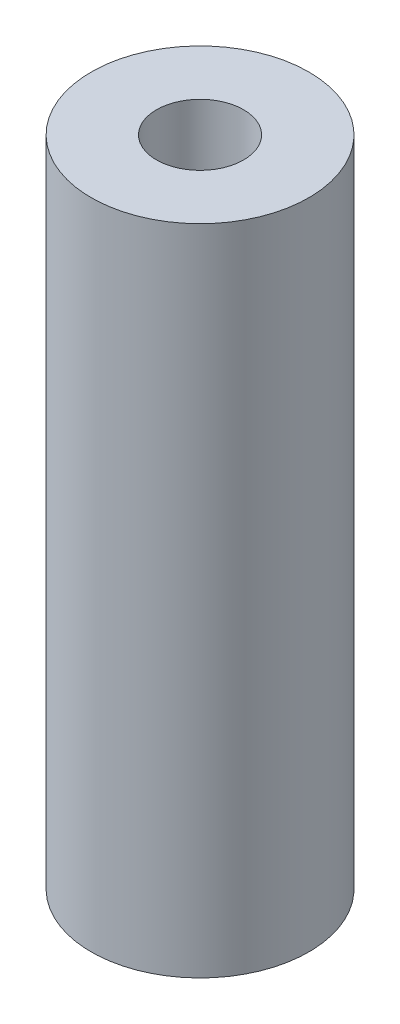
SolidWorks part; units mm, degrees
ref_plane "Front Plane" through (0, 0, 0) normal (0, 0, 1) x (1, 0, 0)
ref_plane "Top Plane" through (0, 0, 0) normal (0, 1, 0) x (1, 0, 0)
ref_plane "Right Plane" through (0, 0, 0) normal (1, 0, 0) x (0, 0, -1)
sketch "Sketch1" plane through (0, 0, 0) normal (0, 1, 0) x (1, 0, 0)
  circle A0 centre (0, 0) radius 7.5
  circle A1 centre (0, 0) radius 3
  dimension "D1" = 6
  dimension "D2" = 15
extrude "Boss-Extrude1" add sketch "Sketch1" along normal blind 45
